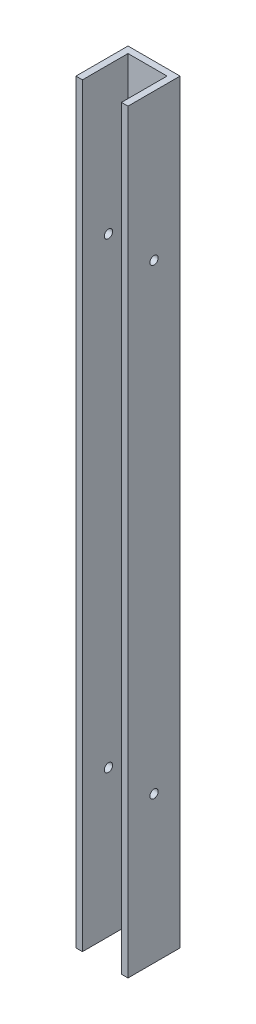
SolidWorks part; units mm, degrees
material "Plain Carbon Steel"
ref_plane "Front Plane" through (0, 0, 0) normal (0, 0, 1) x (1, 0, 0)
ref_plane "Top Plane" through (0, 0, 0) normal (0, 1, 0) x (1, 0, 0)
ref_plane "Right Plane" through (0, 0, 0) normal (1, 0, 0) x (0, 0, -1)
sketch "Sketch1" plane through (0, 0, 0) normal (0, 1, 0) x (1, 0, 0)
  line L0 (0, 0) -> (3.175, 0)
  line L1 (0, 0) -> (0, 25.4)
  line L2 (0, 25.4) -> (25.4, 25.4)
  line L3 (25.4, 25.4) -> (25.4, 0)
  line L4 (25.4, 0) -> (22.225, 0)
  line L5 (22.225, 0) -> (22.225, 22.225)
  line L6 (22.225, 22.225) -> (3.175, 22.225)
  line L7 (3.175, 22.225) -> (3.175, 0)
extrude "Boss-Extrude1" add sketch "Sketch1" along normal blind 368.3 contours L2 L3 L4 L5 L6 L7 L0 L1
sketch "Sketch2" plane through (0, 0, 0) normal (-1, 0, 0) x (0, 0, 1)
  circle A0 centre (-12.7, 71.4375) radius 2.032
  circle A1 centre (-12.7, 296.8625) radius 2.032
extrude "Cut-Extrude1" cut sketch "Sketch2" against normal blind 25.4
